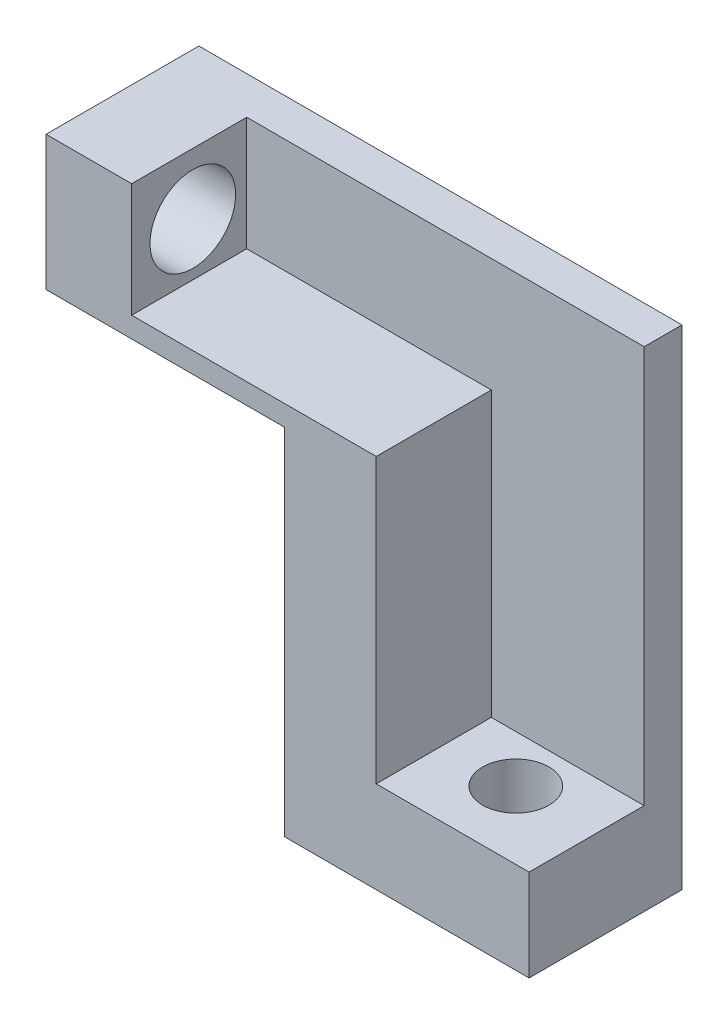
SolidWorks part; units mm, degrees
material "ABS"
ref_plane "Front Plane" through (0, 0, 0) normal (0, 0, 1) x (1, 0, 0)
ref_plane "Top Plane" through (0, 0, 0) normal (0, 1, 0) x (1, 0, 0)
ref_plane "Right Plane" through (0, 0, 0) normal (1, 0, 0) x (0, 0, -1)
sketch "Sketch1" plane through (0, 0, 0) normal (0, 0, 1) x (1, 0, 0)
  line L0 (40, -23.3254) -> (0, -23.3254)
  line L1 (0, -23.3254) -> (0, 34.6746)
  line L7 (15, 56.6746) -> (15, -8.3254)
  line L8 (15, -8.3254) -> (40, -8.3254)
  line L9 (40, -8.3254) -> (40, -23.3254)
  line L10 (15, 56.6746) -> (-39.0028, 56.6746)
  line L11 (-39.0028, 56.6746) -> (-39.0028, 34.6746)
  line L12 (-39.0028, 34.6746) -> (0, 34.6746)
  dimension "D1" = 40
  dimension "D2" = 80
  dimension "D3" = 22
  dimension "D4" = 15
  dimension "D5" = 15
extrude "Boss-Extrude1" add sketch "Sketch1" along normal blind 25
sketch "Sketch2" plane through (0, -8.3254, 0) normal (0, 1, 0) x (1, 0, 0)
  circle A0 centre (26.7302, -13.9013) radius 5.4235
extrude "Cut-Extrude1" cut sketch "Sketch2" against normal blind 30
sketch "Sketch3" plane through (12.4426, 0, 0) normal (1, 0, 0) x (0, 0, -1)
  line L2 (-25, -8.3254) -> (-25, 56.6746) construction
  line L3 (-25, 56.6746) -> (0, 56.6746) construction
  circle A0 centre (-15, 46.6746) radius 7
  point P2 (-14.3988, 46.2898)
  dimension "D1" = 10
  dimension "D2" = 14
  dimension "D3" = 10
extrude "Cut-Extrude2" cut sketch "Sketch3" along normal blind 100 and the other way blind 100
sketch "Sketch5" plane through (15, 0, 0) normal (1, 0, 0) x (0, 0, -1)
  line L0 (-25, 56.6746) -> (0, 56.6746) construction
  line L1 (-30.3369, 56.6746) -> (-6.1823, 56.6746)
  line L2 (-30.3369, 56.6746) -> (-30.3369, 38.0444)
  line L3 (-30.3369, 38.0444) -> (-6.1823, 38.0444)
  line L4 (-6.1823, 56.6746) -> (-6.1823, 38.0444)
extrude "Cut-Extrude3" cut sketch "Sketch5" against normal blind 40
sketch "Sketch6" plane through (15, 0, 0) normal (1, 0, 0) x (0, 0, -1)
  line L0 (0, -8.3254) -> (0, 56.6746) construction
  line L1 (-6.1823, 56.6746) -> (0, 56.6746)
  line L2 (-6.1823, 56.6746) -> (-6.1823, -8.3254)
  line L3 (-6.1823, -8.3254) -> (0, -8.3254)
  line L4 (0, 56.6746) -> (0, -8.3254)
  line L5 (-25, -8.3254) -> (0, -8.3254) construction
extrude "Boss-Extrude2" add sketch "Sketch6" along normal blind 25
